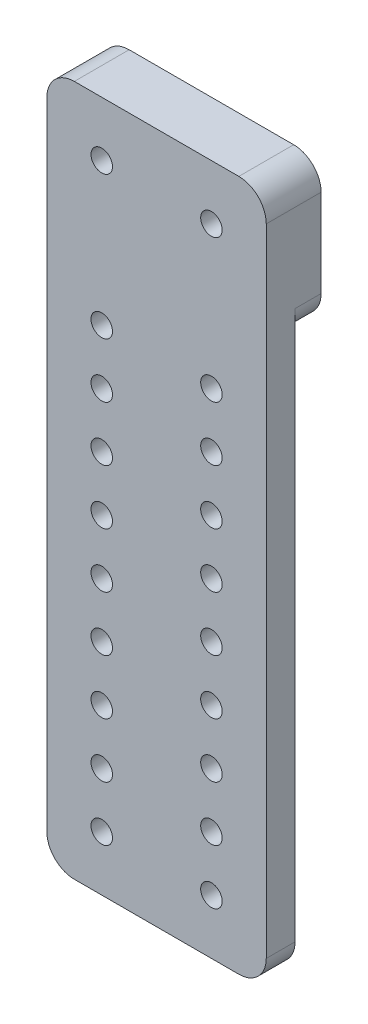
SolidWorks part; units mm, degrees
material "PET"
ref_plane "Front Plane" through (0, 0, 0) normal (0, 0, 1) x (1, 0, 0)
ref_plane "Top Plane" through (0, 0, 0) normal (0, 1, 0) x (1, 0, 0)
ref_plane "Right Plane" through (0, 0, 0) normal (1, 0, 0) x (0, 0, -1)
sketch "Sketch2" plane through (0, 0, 0) normal (0, 0, 1) x (1, 0, 0)
  line L1 (0, 0) -> (50.8, 0)
  line L2 (0, 0) -> (0, 160.02)
  line L3 (0, 160.02) -> (50.8, 160.02)
  line L4 (50.8, 0) -> (50.8, 160.02)
  dimension "D1" = 50.8
  dimension "D2" = 160.02
extrude "Boss-Extrude1" add sketch "Sketch2" against normal blind 12.7
sketch "Sketch3" plane through (0, 0, 0) normal (0, 0, 1) x (1, 0, 0)
  line L0 (50.8, 160.02) -> (0, 160.02) construction
  line L1 (0, 160.02) -> (0, 0) construction
  circle A0 centre (12.7, 147.32) radius 2.4892
  circle A17 centre (38.1, 147.32) radius 2.4892
  circle A24 centre (12.7, 114.3) radius 2.4892
  circle A25 centre (12.7, 101.6) radius 2.4892
  circle A26 centre (12.7, 88.9) radius 2.4892
  circle A27 centre (12.7, 76.2) radius 2.4892
  circle A28 centre (12.7, 63.5) radius 2.4892
  circle A29 centre (12.7, 50.8) radius 2.4892
  circle A30 centre (12.7, 38.1) radius 2.4892
  circle A31 centre (12.7, 25.4) radius 2.4892
  circle A32 centre (12.7, 12.7) radius 2.4892
  circle A33 centre (38.1, 101.6) radius 2.4892
  circle A34 centre (38.1, 88.9) radius 2.4892
  circle A35 centre (38.1, 76.2) radius 2.4892
  circle A36 centre (38.1, 63.5) radius 2.4892
  circle A37 centre (38.1, 50.8) radius 2.4892
  circle A38 centre (38.1, 38.1) radius 2.4892
  circle A39 centre (38.1, 25.4) radius 2.4892
  circle A40 centre (38.1, 12.7) radius 2.4892
  circle A41 centre (38.1, 114.3) radius 2.4892
  dimension "D1" = 4.9784
  dimension "D6" = 4.9784
  dimension "D2" = 12.7
  dimension "D3" = 12.7
  dimension "D7" = 12.7
  dimension "D8" = 33.02
  dimension "D4" = 1
  dimension "D5" = 2
  dimension "D9" = 9
  dimension "D10" = 2
extrude "Cut-Extrude1" cut sketch "Sketch3" against normal through all
fillet "Fillet1" radius 6.35 4 edges at (0, 0, -6.35) (50.8, 0, -6.35) (50.8, 160.02, -6.35) (0, 160.02, -6.35)
sketch "Sketch5" plane through (50.8, 0, 0) normal (1, 0, 0) x (0, 0, -1)
  line L0 (0, 160.02) -> (12.7, 160.02) construction
  line L1 (12.7, 0) -> (6.6675, 0)
  line L2 (12.7, 0) -> (12.7, 127)
  line L3 (12.7, 127) -> (6.6675, 127)
  line L4 (6.6675, 0) -> (6.6675, 127)
  dimension "D1" = 6.0325
  dimension "D2" = 33.02
extrude "Cut-Extrude2" cut sketch "Sketch5" against normal through all
fillet "Fillet2" radius 6.35 2 edges at (0, 127, -9.6837) (50.8, 127, -9.6837)
